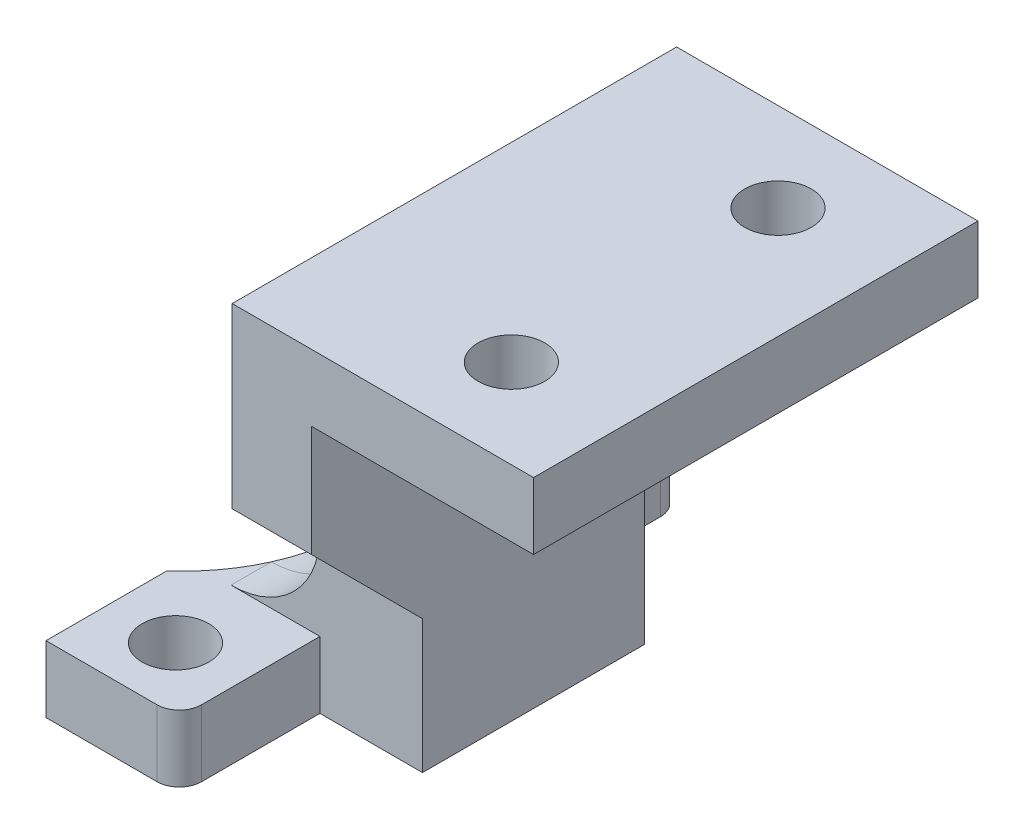
SolidWorks part; units mm, degrees
ref_plane "Front Plane" through (0, 0, 0) normal (0, 0, 1) x (1, 0, 0)
ref_plane "Top Plane" through (0, 0, 0) normal (0, 1, 0) x (1, 0, 0)
ref_plane "Right Plane" through (0, 0, 0) normal (1, 0, 0) x (0, 0, -1)
sketch "Sketch1" plane through (0, 0, 0) normal (0, 1, 0) x (1, 0, 0)
  line L0 (0, 8.5) -> (0, -8.5) construction
  line L1 (-3, -11.3279) -> (3, -11.3279)
  line L2 (-3, -11.3279) -> (-3, 11.3279)
  line L3 (-3, 11.3279) -> (3, 11.3279)
  line L4 (3, -11.3279) -> (3, -5)
  line L5 (-3, -11.3279) -> (3, 11.3279) construction
  line L6 (-3, 11.3279) -> (3, -11.3279) construction
  line L7 (3, -5) -> (7.6154, -5)
  line L8 (7.6154, -5) -> (7.6154, 5)
  line L9 (7.6154, 5) -> (3, 5)
  line L10 (3, 5) -> (3, 11.3279)
  circle A0 centre (0, 8.5) radius 1.5
  circle A1 centre (0, -8.5) radius 1.5
  point P0 (0, 0)
  point P10 (0, 0)
  point P13 (7.6154, 0)
  point P16 (-3, 0)
  dimension "D1" = 3
  dimension "D2" = 17
  dimension "D3" = 6
  dimension "D4" = 10
extrude "Boss-Extrude1" add sketch "Sketch1" along normal blind 3
sketch "Sketch3" plane through (0, 3, 0) normal (0, 1, 0) x (1, 0, 0)
  line L0 (7.6154, 5) -> (3, 5) construction
  line L1 (7.6154, 5) -> (3, 5)
  line L2 (7.6154, 5) -> (7.6154, -5)
  line L3 (7.6154, -5) -> (3, -5)
  line L4 (3, 5) -> (3, -5)
  line L5 (7.6154, -5) -> (7.6154, 5) construction
  line L6 (3, -5) -> (7.6154, -5) construction
extrude "Boss-Extrude2" add sketch "Sketch3" along normal blind 12.9998
fillet "Fillet7" radius 1 2 edges at (3, 1.5, -11.3279) (3, 1.5, 11.3279)
sketch "Sketch7" plane through (0, 0, 0) normal (0, -1, 0) x (1, 0, 0)
  line L0 (-3.6553, -6.3921) -> (-3.7819, 6.4785)
  arc A0 (-3.6553, -6.3921) -> (-3.7819, 6.4785) centre (-8.1114, 0) ccw
extrude "Cut-Extrude4" cut sketch "Sketch7" against normal blind 10
sketch "Sketch9" plane through (0, 15.9998, 0) normal (0, 1, 0) x (1, 0, 0)
  line L1 (4.0509, -10) -> (17.6154, -10)
  line L2 (4.0509, -10) -> (4.0509, 10)
  line L3 (4.0509, 10) -> (17.6154, 10)
  line L4 (17.6154, -10) -> (17.6154, 10)
  line L6 (7.6154, -5) -> (7.6154, 5) construction
  line L7 (7.6154, -5) -> (17.6154, -5) construction
  line L8 (12.6154, -6) -> (12.6154, 6) construction
  circle A0 centre (12.6154, 6) radius 1.5
  circle A1 centre (12.6154, -6) radius 1.5
  point P7 (7.6154, 0)
  point P8 (4.0509, 0)
  point P16 (12.6154, -5)
  point P18 (12.6154, 0)
  dimension "D3" = 3
  dimension "D1" = 20
  dimension "D2" = 10
  dimension "D4" = 12
extrude "Boss-Extrude3" add sketch "Sketch9" along normal blind 3
chamfer "Chamfer1" distance 10 angle 45 1 edges at (5.8332, 15.9998, 5)
chamfer "Chamfer2" distance 10 angle 45 1 edges at (5.8332, 15.9998, -5)
fillet "Fillet8" radius 4 1 edges at (3, 3, 0)
